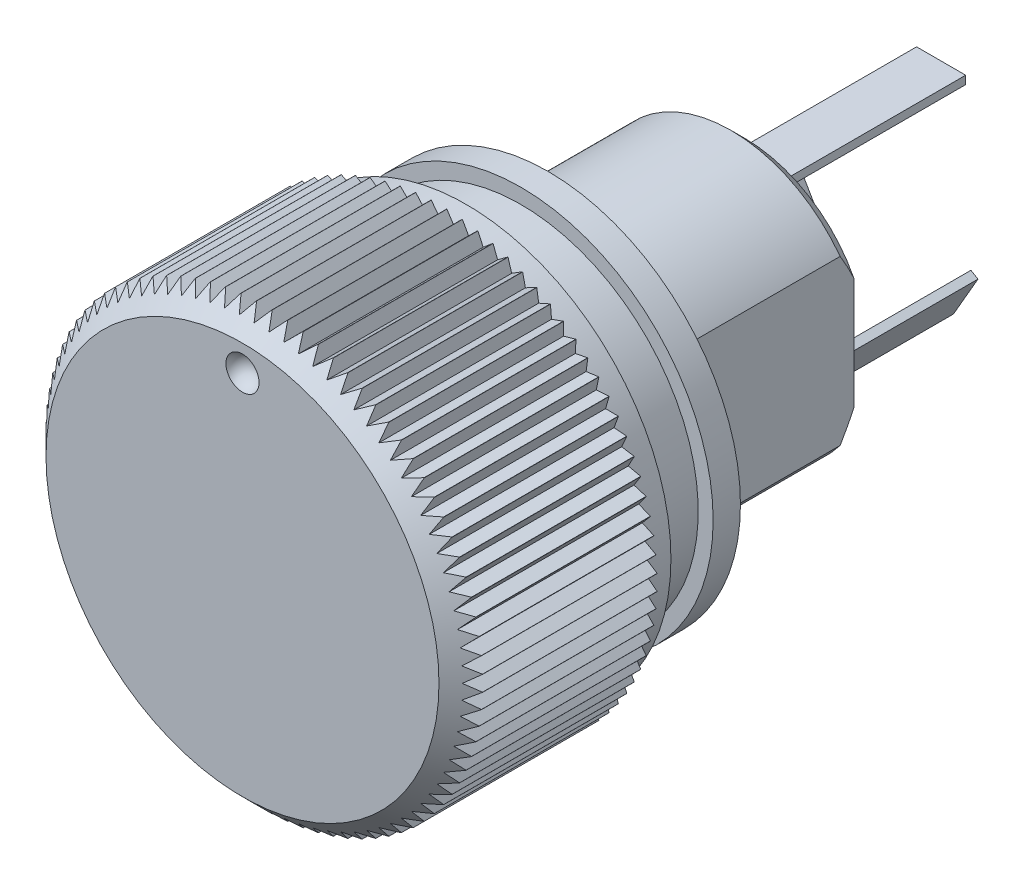
SolidWorks part; units mm, degrees
ref_plane "Front Plane" through (0, 0, 0) normal (0, 0, 1) x (1, 0, 0)
ref_plane "Top Plane" through (0, 0, 0) normal (0, 1, 0) x (1, 0, 0)
ref_plane "Right Plane" through (0, 0, 0) normal (1, 0, 0) x (0, 0, -1)
sketch "Sketch1" plane through (0, 0, 0) normal (0, 0, 1) x (1, 0, 0)
  circle A1 centre (0, 0) radius 8
  dimension "D2" = 16
extrude "Boss-Extrude1" add sketch "Sketch1" along normal blind 10.2
chamfer "Chamfer1" distance 0.8 angle 45 1 edges at (8, 0, 10.2)
sketch "Sketch3" plane through (0, 0, 0) normal (0, 0, -1) x (-1, 0, 0)
  circle A0 centre (0, 0) radius 8.5
  circle A1 centre (0, 0) radius 7.5
extrude "Cut-Extrude1" cut sketch "Sketch3" against normal blind 3
sketch "Sketch4" plane through (0, 0, 0) normal (0, 0, -1) x (-1, 0, 0)
  circle A0 centre (0, 0) radius 7.5
  circle A1 centre (0, 0) radius 6.5
  dimension "D1" = 13
extrude "Cut-Extrude2" cut sketch "Sketch4" against normal blind 2
sketch "Sketch5" plane through (0, 0, 0) normal (0, 0, -1) x (-1, 0, 0)
  circle A0 centre (0, 0) radius 7.0465
extrude "Boss-Extrude2" add sketch "Sketch5" along normal blind 1
sketch "Sketch6" plane through (0, 0, -1) normal (0, 0, -1) x (-1, 0, 0)
  line L0 (-4, 3) -> (-4, -3)
  line L1 (4, 3) -> (4, -3)
  arc A0 (-4, -3) -> (4, -3) centre (0, 0) ccw
  arc A1 (4, 3) -> (-4, 3) centre (0, 0) ccw
  dimension "D1" = 10
  dimension "D2" = 4
  dimension "D3" = 8
extrude "Boss-Extrude3" add sketch "Sketch6" along normal blind 7.2 separate body
chamfer "Chamfer2" distance 0.5 angle 45 2 edges at (0, -5, -8.2) (0, 5, -8.2)
sketch "Sketch7" plane through (0, 0, -8.2) normal (0, 0, -1) x (-1, 0, 0)
  line L0 (3.0914, -0.7456) -> (2.1914, -2.3044)
  line L1 (-0.9, 3.35) -> (0.9, 3.35)
  line L2 (-0.9, 3.35) -> (-0.9, 3.05)
  line L3 (-0.9, 3.05) -> (0.9, 3.05)
  line L4 (0.9, 3.35) -> (0.9, 3.05)
  line L5 (-0.9, 3.35) -> (0.9, 3.05) construction
  line L6 (-0.9, 3.05) -> (0.9, 3.35) construction
  line L7 (3.3512, -0.8956) -> (3.0914, -0.7456)
  line L8 (3.3512, -0.8956) -> (2.4512, -2.4544)
  line L9 (2.4512, -2.4544) -> (2.1914, -2.3044)
  line L10 (-2.1914, -2.3044) -> (-3.0914, -0.7456)
  line L11 (-2.4512, -2.4544) -> (-2.1914, -2.3044)
  line L12 (-2.4512, -2.4544) -> (-3.3512, -0.8956)
  line L13 (-3.3512, -0.8956) -> (-3.0914, -0.7456)
  point P0 (0, 3.2)
  point P9 (2.7713, -1.6)
  point P14 (-2.7713, -1.6)
  point P19 (0, 0)
  dimension "D1" = 0.3
  dimension "D2" = 1.8
  dimension "D3" = 3.2
  dimension "D4" = 3
extrude "Boss-Extrude4" add sketch "Sketch7" along normal blind 7.2 separate body
sketch "Sketch8" plane through (0, 0, -15.4) normal (0, 0, -1) x (-1, 0, 0)
  line L7 (-5.0943, -3.3316) -> (5.6648, -3.3316)
  line L8 (-5.0943, -3.3316) -> (-5.0943, 0.377)
  line L9 (-5.0943, 0.377) -> (5.6648, 0.377)
  line L10 (5.6648, -3.3316) -> (5.6648, 0.377)
extrude "Cut-Extrude3" cut sketch "Sketch8" against normal blind 2
sketch "Sketch9" plane through (0, 0, 10.2) normal (0, 0, 1) x (1, 0, 0)
  circle A0 centre (0, 6.2456) radius 0.6059
extrude "Cut-Extrude4" cut sketch "Sketch9" against normal blind 0.5
fillet "Fillet1" radius 0.6 1 edges at (0.6059, 6.2456, 9.7)
sketch "Sketch10" plane through (0, 0, 10.2) normal (0, 0, 1) x (1, 0, 0)
  line L0 (0, 7.2) -> (0, 8.4603) construction
  line L1 (0, 7.6257) -> (-0.3403, 8.0711)
  line L2 (-0.3403, 8.0711) -> (0.3403, 8.0711)
  line L3 (0, 7.6257) -> (0.3403, 8.0711)
  circle A0 centre (0, 0) radius 7.2 construction
  point P10 (0, 8.0711)
  point P255 (0, 0)
extrude "Cut-Extrude5" cut sketch "Sketch10" against normal through all
pattern_circular "CirPattern1" count 88 over 360 about axis through (0, 0, 10.2) along (0, 0, 1) of "Cut-Extrude5"
